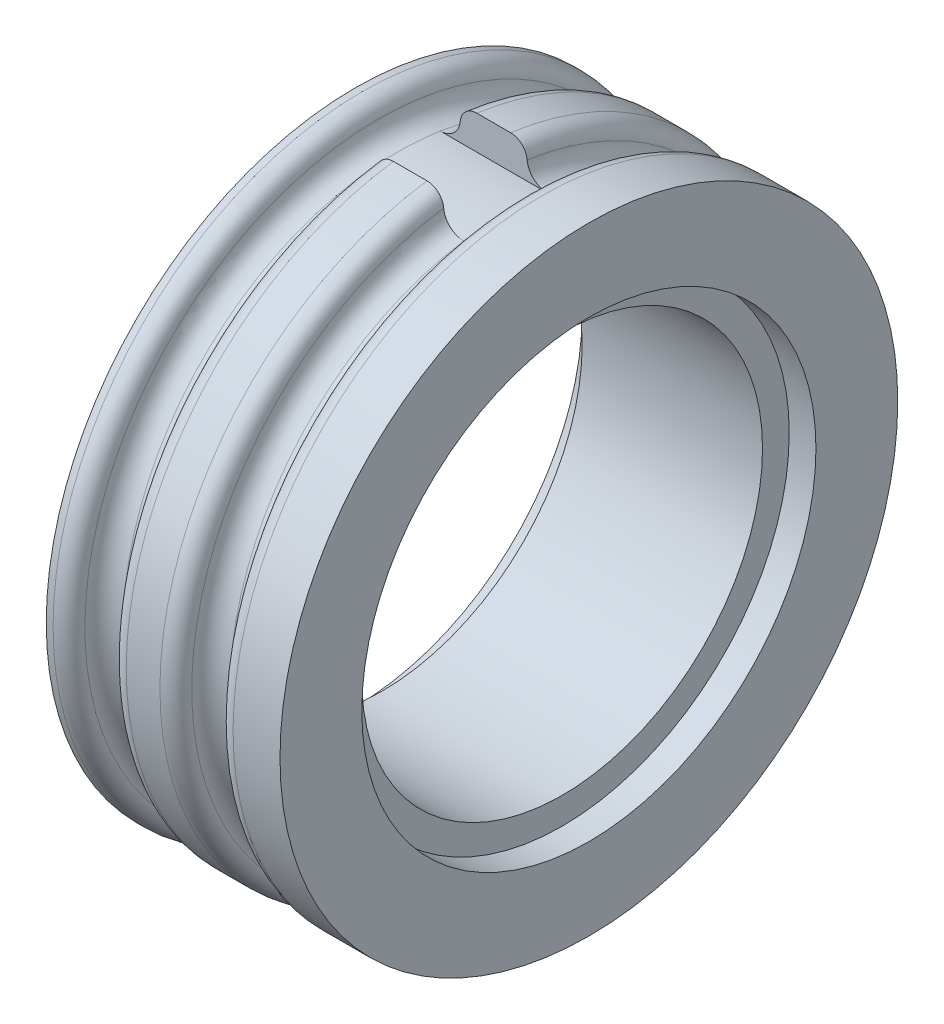
SolidWorks part; units mm, degrees
ref_plane "Front Plane" through (0, 0, 0) normal (0, 0, 1) x (1, 0, 0)
ref_plane "Top Plane" through (0, 0, 0) normal (0, 1, 0) x (1, 0, 0)
ref_plane "Right Plane" through (0, 0, 0) normal (1, 0, 0) x (0, 0, -1)
sketch "Sketch2" plane through (0, 0, 0) normal (0, 1, 0) x (1, 0, 0)
  line L1 (0, 6) -> (7, 6)
  line L3 (7, 0) -> (0, 0)
  line L4 (0, 6) -> (0, 9.25)
  line L5 (0, 9.25) -> (0.7, 9.25)
  line L6 (0.7, 9.25) -> (0.7, 8.25)
  line L7 (0.7, 8.25) -> (1.9, 8.25)
  line L8 (1.9, 8.25) -> (1.9, 9.25)
  line L9 (1.9, 9.25) -> (3.9, 9.25)
  line L10 (3.9, 9.25) -> (3.9, 8.25)
  line L11 (3.9, 8.25) -> (5.1, 8.25)
  line L12 (5.1, 8.25) -> (5.1, 9.25)
  line L13 (5.1, 9.25) -> (7, 9.25)
  line L14 (7, 9.25) -> (7, 6)
  point P13 (4.5, 8.25)
  dimension "D1" = 6
  dimension "D2" = 7
  dimension "D3" = 8.25
  dimension "D4" = 1.2
  dimension "D5" = 1.2
  dimension "D6" = 2
  dimension "D7" = 2.5
  dimension "D8" = 1
revolve "Revolve1" add sketch "Sketch2" angle 360 about L3 region at (3.5708, 0, -7.4923)
ref_plane "Plane1" through (0, 10, 0) normal (0, 1, 0) x (1, 0, 0)
sketch "Sketch7" plane through (0, 10, 0) normal (0, 1, 0) x (1, 0, 0)
  line L0 (5.1, 8.25) -> (5.1, -8.25) construction
  line L1 (0.7, -8.25) -> (0.7, 8.25) construction
  line L2 (3.9, -8.25) -> (3.9, 8.25) construction
  line L3 (1.9, 8.25) -> (1.9, -8.25) construction
  line L4 (5.1, 8.25) -> (5.1, -8.25) construction
  line L5 (0.7, -8.25) -> (0.7, 8.25) construction
  line L6 (3.9, -8.25) -> (3.9, 8.25) construction
  line L7 (1.9, 8.25) -> (1.9, -8.25) construction
  line L9 (1.9, -1.25) -> (3.9, -1.25)
  line L10 (1.9, -1.25) -> (1.9, 1.25)
  line L11 (1.9, 1.25) -> (3.9, 1.25)
  line L12 (3.9, -1.25) -> (3.9, 1.25)
  point P12 (1.9, 0)
  point P13 (0, 0)
  dimension "D1" = 2.5
extrude "Cut-Extrude3" cut sketch "Sketch7" against normal up to surface (1.8452 mm away) up to face at (1.9, 0, -8.25)
fillet "Fillet1" radius 0.6 4 edges at (5.1, 0, -8.25) (3.9, -8.25, 0) (1.9, -8.25, 0) (0.7, 0, -8.25)
sketch "Sketch3" plane through (7, 0, 0) normal (1, 0, 0) x (0, 0, -1)
  circle A0 centre (0, 0) radius 6.8
  dimension "D1" = 13.6
extrude "Cut-Extrude1" cut sketch "Sketch3" against normal blind 0.8
sketch "Sketch4" plane through (0, 0, 0) normal (-1, 0, 0) x (0, 0, 1)
  circle A0 centre (0, 0) radius 6.8 construction
  circle A1 centre (0, 0) radius 6.8
extrude "Cut-Extrude2" cut sketch "Sketch4" against normal blind 0.8
fillet "Fillet2" radius 0.5 4 edges at (5.1, 0, -9.25) (3.9, -9.25, 0) (1.9, -9.25, 0) (0.7, 0, -9.25)
